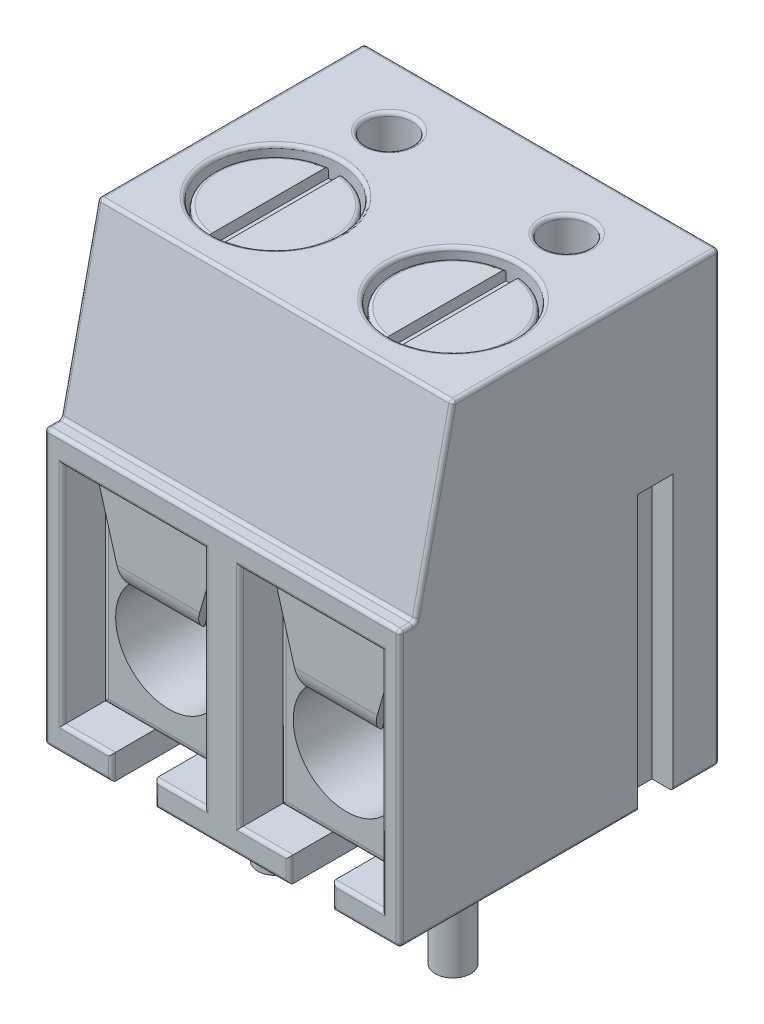
SolidWorks part; units mm, degrees
ref_plane "Front" through (0, 0, 0) normal (0, 0, 1) x (1, 0, 0)
ref_plane "Top" through (0, 0, 0) normal (0, 1, 0) x (1, 0, 0)
ref_plane "Right" through (0, 0, 0) normal (1, 0, 0) x (0, 0, -1)
sketch "Эскиз1" plane through (0, 0, 0) normal (0, 0, 1) x (1, 0, 0)
  line L1 (-5, -6.3) -> (5, -6.3)
  line L2 (-5, -6.3) -> (-5, 6.3)
  line L3 (-5, 6.3) -> (5, 6.3)
  line L4 (5, -6.3) -> (5, 6.3)
  line L5 (-5, -6.3) -> (5, 6.3) construction
  line L6 (-5, 6.3) -> (5, -6.3) construction
  point P0 (0, 0)
  dimension "D1" = 12.6
  dimension "D2" = 10
extrude "Бобышка-Вытянуть1" add sketch "Эскиз1" along normal blind 9
sketch "Эскиз2" plane through (5, 0, 0) normal (1, 0, 0) x (0, 0, -1)
  line L0 (-9, 1.4378) -> (-8.64, 1.4378)
  line L1 (-9, -6.3) -> (-9, 6.3) construction
  line L2 (-8.5423, 1.5165) -> (-7.5, 6.3)
  line L3 (-9, 6.3) -> (0, 6.3) construction
  line L4 (-7.5, 6.3) -> (-9, 6.3)
  line L5 (-9, 6.3) -> (-9, 1.4378)
  arc A0 (-8.64, 1.4378) -> (-8.5423, 1.5165) centre (-8.64, 1.5378) ccw
  dimension "D1" = 0.1
  dimension "D2" = 1.5
  dimension "D3" = 4.8622
  dimension "D4" = 77.708
extrude "Вырез-Вытянуть1" cut sketch "Эскиз2" against normal through all
sketch "Эскиз4" plane through (0, 0, 9) normal (0, 0, 1) x (1, 0, 0)
  line L0 (0, 6.3) -> (0, -6.3) construction
  line L1 (-5, 6.3) -> (5, 6.3) construction
  line L2 (-5, -6.3) -> (5, -6.3) construction
  line L4 (-5, 1.4378) -> (5, 1.4378) construction
  line L5 (-4.5, -5.6) -> (-0.5, -5.6)
  line L6 (-4.5, -5.6) -> (-4.5, 0.7378)
  line L7 (-4.5, 0.7378) -> (-0.5, 0.7378)
  line L8 (-0.5, -5.6) -> (-0.5, 0.7378)
  line L9 (-4.5, -5.6) -> (-0.5, 0.7378) construction
  line L11 (-4.5, 0.7378) -> (-0.5, -5.6) construction
  line L12 (-5, 1.4378) -> (-5, -6.3) construction
  line L13 (4.5, 0.7378) -> (0.5, -5.6) construction
  line L14 (4.5, -5.6) -> (0.5, 0.7378) construction
  line L15 (0.5, -5.6) -> (0.5, 0.7378)
  line L16 (4.5, 0.7378) -> (0.5, 0.7378)
  line L17 (4.5, -5.6) -> (4.5, 0.7378)
  line L18 (4.5, -5.6) -> (0.5, -5.6)
  point P6 (-2.5, -2.4311)
  point P19 (2.5, -2.4311)
  dimension "D1" = 0.7
  dimension "D2" = 0.5
  dimension "D3" = 0.5
  dimension "D4" = 0.7
extrude "Вырез-Вытянуть2" cut sketch "Эскиз4" against normal blind 1
sketch "Эскиз6" plane through (0, 0, 9) normal (0, 0, 1) x (1, 0, 0)
  line L0 (-0.5, 0.7378) -> (-4.5, 0.7378) construction
  line L1 (-4.5, 0.7378) -> (-4.5, -5.6) construction
  line L2 (-0.5, -5.6) -> (-0.5, 0.7378) construction
  line L3 (-4.5, -5.6) -> (-0.5, -5.6) construction
  line L4 (-0.5, 0.7378) -> (-4.5, 0.7378)
  line L5 (-4.5, 0.7378) -> (-4.5, -5.6)
  line L6 (-0.5, -5.6) -> (-0.5, 0.7378)
  line L7 (-4.5, -5.6) -> (-3.1, -5.6)
  line L8 (-0.6, 0.6378) -> (-4.4, 0.6378)
  line L9 (-4.4, 0.6378) -> (-4.4, -5.5)
  line L10 (-4.4, -5.5) -> (-0.6, -5.5)
  line L11 (-0.6, -5.5) -> (-0.6, 0.6378)
  line L12 (-2.5, 0.6378) -> (-2.5, -8.4565) construction
  line L15 (-3.1, -5.6) -> (-3.1, -6.3)
  line L16 (-5, -6.3) -> (5, -6.3) construction
  line L17 (-3.1, -6.3) -> (-1.9, -6.3)
  line L18 (-1.9, -6.3) -> (-1.9, -5.6)
  line L19 (-1.9, -5.6) -> (-0.5, -5.6)
  line L20 (-4.5, -5.6) -> (-0.5, -5.6) construction
  line L21 (0, -6.3) -> (0, 1.4378) construction
  line L22 (-5, 1.4378) -> (5, 1.4378) construction
  line L23 (1.9, -5.6) -> (0.5, -5.6)
  line L24 (1.9, -6.3) -> (1.9, -5.6)
  line L25 (3.1, -6.3) -> (1.9, -6.3)
  line L26 (3.1, -5.6) -> (3.1, -6.3)
  line L27 (0.6, -5.5) -> (0.6, 0.6378)
  line L28 (4.4, -5.5) -> (0.6, -5.5)
  line L29 (4.4, 0.6378) -> (4.4, -5.5)
  line L30 (0.6, 0.6378) -> (4.4, 0.6378)
  line L31 (4.5, -5.6) -> (3.1, -5.6)
  line L32 (0.5, -5.6) -> (0.5, 0.7378)
  line L33 (4.5, 0.7378) -> (4.5, -5.6)
  line L34 (0.5, 0.7378) -> (4.5, 0.7378)
  dimension "D2" = 0.6
  dimension "D3" = 0.6
  dimension "D1" = 0.1
extrude "Вырез-Вытянуть4" cut sketch "Эскиз6" against normal blind 4.6
sketch "Эскиз7" plane through (0, -5.5, 0) normal (0, -1, 0) x (1, 0, 0)
  line L0 (-5, 9) -> (-5, 0) construction
  line L1 (5, 9) -> (5, 0) construction
  line L2 (-5, 0) -> (5, 0) construction
  circle A0 centre (-2.5, 5) radius 0.5
  circle A1 centre (2.5, 5) radius 0.5
  dimension "D1" = 1
  dimension "D2" = 2.5
  dimension "D3" = 2.5
  dimension "D4" = 5
extrude "Бобышка-Вытянуть3" add sketch "Эскиз7" along normal blind 4.4
sketch "Эскиз8" plane through (0, 0, 8) normal (0, 0, 1) x (1, 0, 0)
  line L0 (-4.4, -5.5) -> (-0.6, -5.5) construction
  line L1 (-4.4, -5.5) -> (-4.4, 0.6378) construction
  line L2 (4.4, -5.5) -> (4.4, 0.6378) construction
  circle A0 centre (-2.5, -3.2) radius 1.5
  circle A1 centre (2.5, -3.2) radius 1.5
  dimension "D1" = 3
  dimension "D2" = 2.3
  dimension "D3" = 1.9
  dimension "D4" = 1.9
extrude "Вырез-Вытянуть5" cut sketch "Эскиз8" against normal blind 3.4
sketch "Эскиз9" plane through (0, 0, 8) normal (0, 0, 1) x (1, 0, 0)
  line L0 (-4.3454, 0.7378) -> (-3.5, -2.1896)
  line L1 (-0.5, 0.7378) -> (-4.5, 0.7378) construction
  line L2 (-2.5, -3.2) -> (-2.5, 3.2022) construction
  line L3 (-4.3454, 0.7378) -> (-0.6546, 0.7378)
  line L4 (-0.5, 0.7378) -> (-4.5, 0.7378) construction
  line L5 (-3.5, -2.1896) -> (-1.5, -2.1896)
  line L6 (-0.6546, 0.7378) -> (-1.5, -2.1896)
  line L7 (0, 4.0687) -> (0, -6.3) construction
  line L8 (-1.9, -6.3) -> (1.9, -6.3) construction
  line L9 (0.6546, 0.7378) -> (1.5, -2.1896)
  line L10 (3.5, -2.1896) -> (1.5, -2.1896)
  line L11 (4.3454, 0.7378) -> (0.6546, 0.7378)
  line L12 (4.3454, 0.7378) -> (3.5, -2.1896)
  point P12 (-2.5, -2.1896)
  point P13 (-2.5, 0.7378)
  point P21 (2.5, 0.7378)
  point P22 (2.5, -2.1896)
  dimension "D1" = 1.8454
  dimension "D2" = 2
  dimension "D3" = 2.9273
extrude "Бобышка-Вытянуть4" add sketch "Эскиз9" along normal blind 0.3
fillet "Скругление1" radius 0.7 2 edges at (2.5, -2.1896, 8.3) (-2.5, -2.1896, 8.3)
fillet "Скругление2" radius 0.2 6 edges at (0.6, -2.4311, 8) (4.4, -2.4311, 8) (2.5, -5.5, 8) (-0.6, -2.4311, 8) (-4.4, -2.4311, 8) (-2.5, -5.5, 8)
sketch "Эскиз10" plane through (0, 6.3, 0) normal (0, 1, 0) x (1, 0, 0)
  line L0 (0, 0) -> (0, -7.5) construction
  line L1 (-5, -7.5) -> (5, -7.5) construction
  line L2 (5, 0) -> (-5, 0) construction
  circle A0 centre (-2.5, -5) radius 1.8
  circle A1 centre (-2.5, -1.8) radius 0.65
  circle A2 centre (2.5, -1.8) radius 0.65
  circle A3 centre (2.5, -5) radius 1.8
  dimension "D1" = 3.6
  dimension "D4" = 1.3
  dimension "D2" = 2.5
  dimension "D3" = 2.5
  dimension "D5" = 1.8
extrude "Вырез-Вытянуть6" cut sketch "Эскиз10" against normal blind 1
sketch "Эскиз11" plane through (0, 5.3, 0) normal (0, 1, 0) x (1, 0, 0)
  circle A0 centre (-2.5, -5) radius 1.7
  circle A1 centre (2.5, -5) radius 1.7
  dimension "D2" = 3.4
extrude "Бобышка-Вытянуть6" add sketch "Эскиз11" along normal blind 0.8
sketch "Эскиз12" plane through (0, 6.1, 0) normal (0, 1, 0) x (1, 0, 0)
  line L0 (-2.5, -3.3) -> (-2.5, -6.7) construction
  line L1 (-2.7, -3.3118) -> (-2.7, -6.6882)
  line L2 (-2.3, -3.3118) -> (-2.3, -6.6882)
  line L3 (0, 0) -> (0, -7.5) construction
  line L4 (-5, -7.5) -> (5, -7.5) construction
  line L5 (2.5, -3.3) -> (2.5, -6.7) construction
  line L6 (2.3, -3.3118) -> (2.3, -6.6882)
  line L7 (2.7, -3.3118) -> (2.7, -6.6882)
  circle A0 centre (-2.5, -5) radius 1.7 construction
  arc A1 (-2.7, -6.6882) -> (-2.3, -6.6882) centre (-2.5, -5) ccw
  arc A2 (-2.3, -3.3118) -> (-2.7, -3.3118) centre (-2.5, -5) ccw
  arc A3 (2.3, -3.3118) -> (2.7, -3.3118) centre (2.5, -5) cw
  arc A4 (2.7, -6.6882) -> (2.3, -6.6882) centre (2.5, -5) cw
  dimension "D1" = 0.2
extrude "Вырез-Вытянуть7" cut sketch "Эскиз12" against normal blind 0.3
sketch "Эскиз15" plane through (-5, 0, 0) normal (-1, 0, 0) x (0, 0, 1)
  line L0 (1.3, -6.3) -> (1.3, 1.4378)
  line L1 (9, -6.3) -> (0, -6.3) construction
  line L2 (1.3, 1.4378) -> (2.3, 1.4378)
  line L3 (2.3, 1.4378) -> (2.3, -6.3)
  line L4 (2.3, -6.3) -> (1.3, -6.3)
  line L5 (9, 1.4378) -> (8.64, 1.4378) construction
  line L6 (0, 6.3) -> (0, -6.3) construction
  dimension "D1" = 1
  dimension "D2" = 1.3
extrude "Бобышка-Вытянуть8" add sketch "Эскиз15" along normal blind 0.6
sketch "Эскиз16" plane through (5, 0, 0) normal (1, 0, 0) x (0, 0, -1)
  line L0 (-2.3, -6.3) -> (-2.3, 1.4378)
  line L1 (-2.3, 1.4378) -> (-1.3, 1.4378)
  line L2 (-1.3, 1.4378) -> (-1.3, -6.3)
  line L3 (-1.3, -6.3) -> (-2.3, -6.3)
extrude "Вырез-Вытянуть8" cut sketch "Эскиз16" against normal blind 0.6
fillet "Скругление3" radius 0.1 43 edges at (-5, 1.4378, 8.82) (-5, 1.4599, 8.5772) (5, 1.4378, 8.82) (5, 1.4599, 8.5772) (-1.9, -5.95, 9) (-1.2, -5.6, 9) (-0.5, -2.4311, 9) (-2.5, 0.7378, 9) (-4.5, -2.4311, 9) (-3.1, -5.95, 9) (-4.05, -6.3, 9) (-5, -2.4311, 9) (0, 1.4378, 9) (5, -2.4311, 9) (4.05, -6.3, 9) (3.1, -5.95, 9) (1.2, -5.6, 9) (4.5, -2.4311, 9) (2.5, 0.7378, 9) (0.5, -2.4311, 9) (1.9, -5.95, 9) (0, -6.3, 9) (2.5, 6.3, 3.2) (-2.5, 6.3, 6.8) (2.5, 6.3, 1.15) (-2.5, 6.3, 2.45) (5, -6.3, 0.65) (5, -6.3, 5.65) (5, 0, 0) (0, -6.3, 0) (-5, 0, 0) (-5, 3.9082, 8.0211) (5, 3.9082, 8.0211) (0, 6.3, 7.5) (5, 6.3, 3.75) (0, 6.3, 0) (-5, 6.3, 3.75) (4.2, 6.1, 5) (0.8, 6.1, 5) (-0.8, 6.1, 5) (-4.2, 6.1, 5)
fillet "Скругление4" radius 0.4 4 edges at (1.9, -5.95, 4.4) (3.1, -5.95, 4.4) (-1.9, -5.95, 4.4) (-3.1, -5.95, 4.4)
